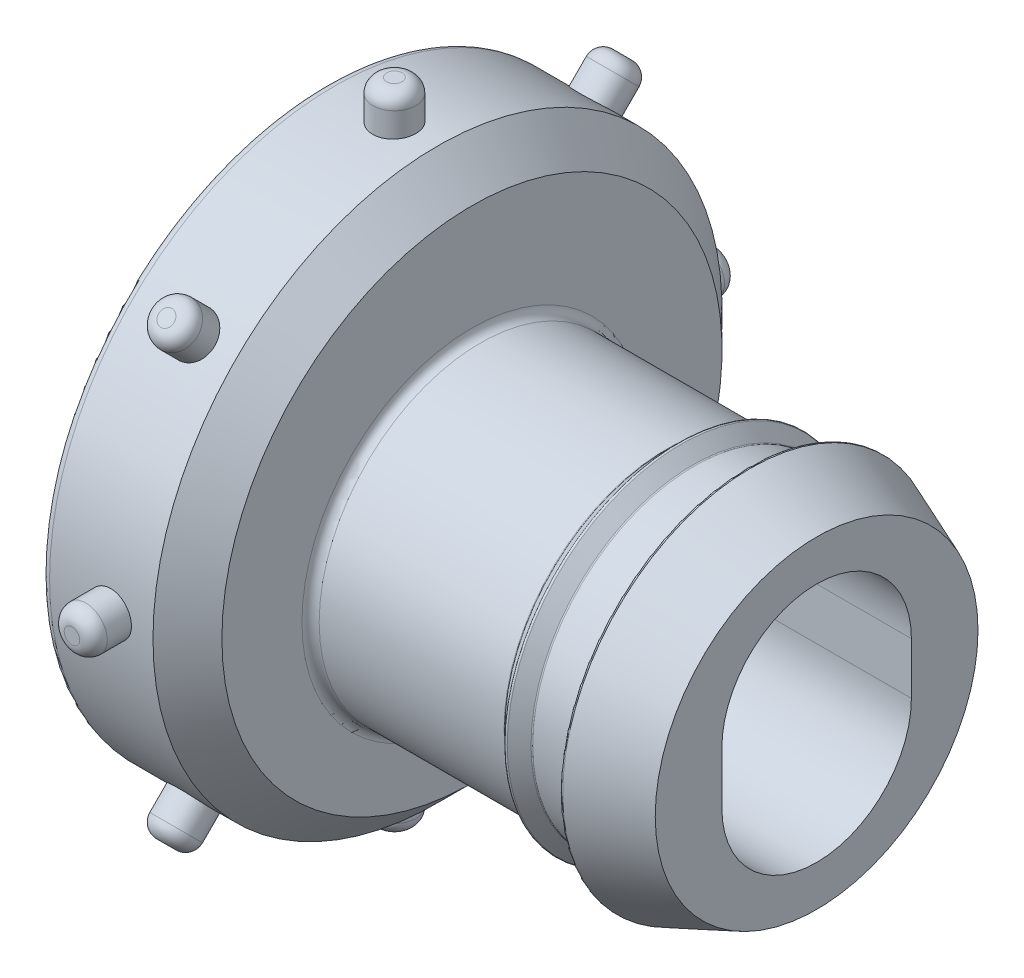
SolidWorks part; units mm, degrees
note: '?' marks a value the reader was unsure of. The reader was unsure of these and kept them because the rebuilt part matched: shared geometry of "Sketch2<3>".
ref_plane "Front Plane" through (0, 0, 0) normal (0, 0, 1) x (1, 0, 0)
ref_plane "Top Plane" through (0, 0, 0) normal (0, 1, 0) x (1, 0, 0)
ref_plane "Right Plane" through (0, 0, 0) normal (1, 0, 0) x (0, 0, -1)
sketch "Sketch1" plane through (0, 0, 0) normal (0, 1, 0) x (1, 0, 0)
  line L0 (0, 0) -> (-20, 0)
  line L1 (0, 0) -> (0, 9.365)
  line L2 (0, 9.365) -> (-3.97, 10.955)
  line L3 (-3.97, 10.955) -> (-3.97, 9.365)
  line L4 (0, 9.365) -> (-19.3321, 9.365) construction
  line L5 (-3.97, 9.365) -> (-7.15, 9.365)
  line L6 (-7.15, 9.365) -> (-7.94, 10.155)
  line L7 (-7.94, 10.155) -> (-8.73, 9.365)
  line L8 (-8.73, 9.365) -> (-20, 9.365)
  line L9 (-20, 9.365) -> (-20, 0)
  dimension "D1" = 20
  dimension "D2" = 9.365
  dimension "D3" = 1.59
  dimension "D4" = 3.97
  dimension "D5" = 7.94
  dimension "D6" = 0.79
revolve "Revolve1" add sketch "Sketch1" angle 360 about L0
sketch "Sketch2" plane through (-20, 0, 0) normal (-1, 0, 0) x (0, 0, 1)
  line L0 (0, 0) -> (0, 4.1864) construction
  line L1 (5.5, 1.5) -> (5.5, 0)
  line L3 (-5.5, 1.5) -> (-5.5, 0)
  line L4 (5.5, 0) -> (5.5, -1.5)
  line L5 (-5.5, -1.5) -> (-5.5, 0)
  circle A0 centre (0, 1.5) radius 9.365
  arc A1 (-5.5, 0) -> (-5.4486, -0.75) centre (0, 0) ccw
  circle A3 centre (0, 1.5) radius 16.51
  circle A4 centre (0, 0) radius 9.365 construction
  arc A6 (5.5, 1.5) -> (-5.5, 1.5) centre (0, 1.5) ccw
  arc A7 (-5.5, -1.5) -> (5.5, -1.5) centre (0, -1.5) ccw
  dimension "D1" = 11
  dimension "D2" = 33.02
  dimension "D3" = 1.5
  dimension "D4" = 1.5
extrude "Boss-Extrude1" add sketch "Sketch2" along normal blind 8.5
ref_axis "Axis1" through (-28.5, -17.1251, 0) along (0, 1, 0)?
sketch "Sketch4" plane through (-28.5, 0, 0) normal (-1, 0, 0) x (0, 0, 1)
  line L0 (0, -17.1251) -> (0, 19.1969) construction
  line L1 (9.09, 7.6298) -> (-9.09, 7.6298)
  line L2 (9.09, 7.6298) -> (9.09, -5.5702)
  line L3 (9.09, -5.5702) -> (-9.09, -5.5702)
  line L4 (-9.09, 7.6298) -> (-9.09, -5.5702)
  point P6 (0, 7.6298)
  dimension "D1" = 18.18
  dimension "D2" = 13.2
extrude "Cut-Extrude1" cut sketch "Sketch4" against normal blind 7
sketch "Sketch5" plane through (-28.5, 0, 0) normal (-1, 0, 0) x (0, 0, 1)
  line L0 (0, -17.1251) -> (0, 19.1969) construction
  circle A0 centre (0, 1.5) radius 14.14
  dimension "D1" = 28.28
  dimension "D2" = 1.5
sketch "Sketch6" plane through (0, 0, 0) normal (0, 0, 1) x (1, 0, 0)
  line L0 (-28.5, 15.64) -> (-28.5, -12.64) construction
  circle A0 centre (-28.5, 15.64) radius 0.9
  point P0 (-28.5, 15.64)
  dimension "D1" = 1.8
ref_axis "Axis2" through (-28.5, 1.5, 0) along (1, 0, 0)
revolve "Cut-Revolve1" cut sketch "Sketch6" angle 360 about axis through (-28.5, 1.5, 0) along (1, 0, 0)
ref_plane "Plane1" through (-24.5, 0, 0) normal (-1, 0, 0) x (0, 0, 1)
ref_axis "Axis3" through (-24.5, -18.3, 0) along (0, 1, 0)?
ref_plane "Plane2" through (0, 18.01, 0) normal (0, 1, 0) x (1, 0, 0)
sketch "Sketch7" plane through (0, 18.01, 0) normal (0, 1, 0) x (1, 0, 0)
  circle A0 centre (-24.5, 0) radius 1.25
  dimension "D1" = 2.5
extrude "Boss-Extrude2" add sketch "Sketch7" along normal blind 2.2 and the other way blind 2 contours A0
fillet "Fillet2" radius 0.8 1 edges at (-24.5, 20.21, 1.25)
pattern_circular "CirPattern1" count 8 over 360 about axis through (0, 1.5, 0) along (1, 0, 0) of "Boss-Extrude2", "Fillet2"
fillet "Fillet4" radius 0.1 5 edges at (-8.73, 0, -9.365) (-7.94, 0, -10.155) (-7.15, 0, -9.365) (-3.97, 0, -9.365) (-3.97, 0, -10.955)
extrude "Cut-Extrude2" cut sketch "Sketch2<3>" against normal through all both and the other way through all
sketch "Sketch2<3>" plane through (-20, 0, 0) normal (-1, 0, 0) x (0, 0, 1) same geometry as "Sketch2"
sketch "Sketch8" plane through (-21.5, 0, 0) normal (-1, 0, 0) x (0, 0, 1)
  line L0 (-5.5, 1.5) -> (-5.5, -1.5) construction
  line L1 (-9.09, -5.5702) -> (-5.5, -5.5702)
  line L2 (-9.09, -5.5702) -> (-9.09, 2.0798)
  line L3 (-9.09, 2.0798) -> (-5.5, 2.0798)
  line L4 (-5.5, -5.5702) -> (-5.5, 2.0798)
  line L9 (5.5, -1.5) -> (5.5, 1.5) construction
  line L13 (9.09, -5.5702) -> (5.5, -5.5702)
  line L14 (9.09, -5.5702) -> (9.09, 2.0798)
  line L15 (9.09, 2.0798) -> (5.5, 2.0798)
  line L16 (5.5, -5.5702) -> (5.5, 2.0798)
  dimension "D1" = 7.65
extrude "Boss-Extrude3" add sketch "Sketch8" along normal blind 0.64
fillet "Fillet5" radius 0.5 2 edges at (-22.14, 2.0798, 7.295) (-22.14, -1.7452, 5.5)
fillet "Fillet6" radius 0.5 1 edges at (-20, 0, 9.365)
chamfer "Chamfer1" distance 2 angle 45 1 edges at (-20, 1.5, 16.51)
fillet "Fillet7" radius 1 1 edges at (-28.5, 1.5, -13.24)
chamfer "Chamfer2" distance 1 distance2 6 1 edges at (-28.5, 7.6298, 0)
fillet "Fillet8" radius 0.5 1 edges at (-28.5, 1.5, 16.51)
equation "\"WallThick\"= 1.2'thickness of wall for printer"
equation "\"dHole\"= 3.3'diameter of screw hole"
equation "\"D1@Boss-Extrude2\"=(37.42-33.02)/2"
